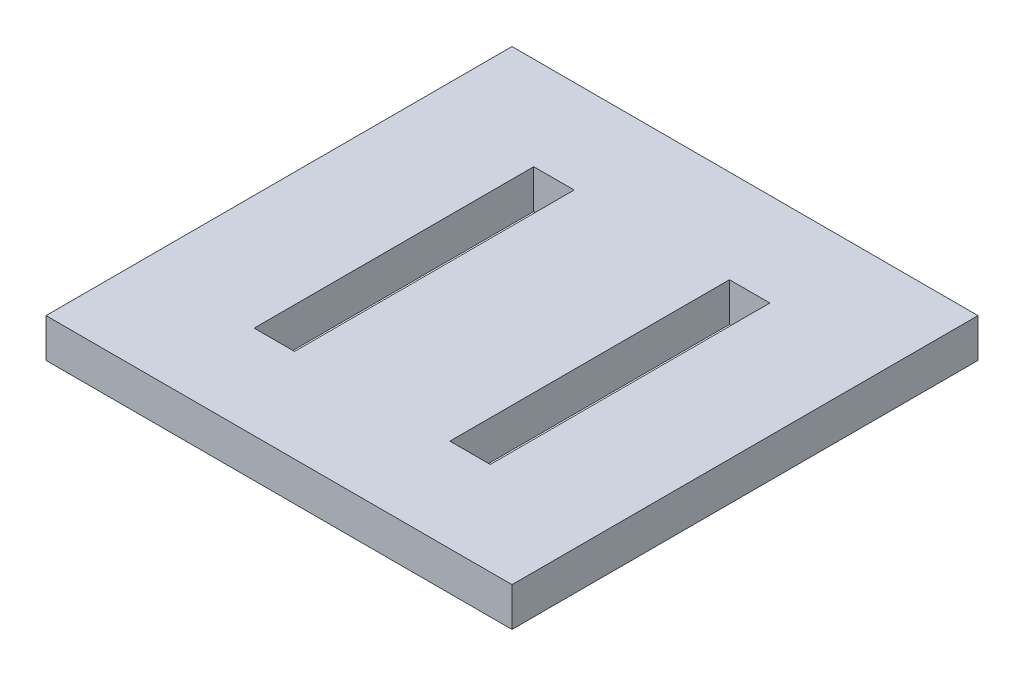
SolidWorks part; units mm, degrees
material "Plain Carbon Steel"
ref_plane "Front Plane" through (0, 0, 0) normal (0, 0, 1) x (1, 0, 0)
ref_plane "Top Plane" through (0, 0, 0) normal (0, 1, 0) x (1, 0, 0)
ref_plane "Right Plane" through (0, 0, 0) normal (1, 0, 0) x (0, 0, -1)
sketch "Sketch1" plane through (0, 0, 0) normal (0, 1, 0) x (1, 0, 0)
  line L1 (-38.1, -38.1) -> (38.1, -38.1)
  line L2 (-38.1, -38.1) -> (-38.1, 38.1)
  line L3 (-38.1, 38.1) -> (38.1, 38.1)
  line L4 (38.1, -38.1) -> (38.1, 38.1)
  line L5 (-38.1, -38.1) -> (38.1, 38.1) construction
  line L6 (-38.1, 38.1) -> (38.1, -38.1) construction
  point P0 (0, 0)
  point P6 (0, 38.1)
  dimension "D1" = 76.2
  dimension "D2" = 76.2
extrude "Boss-Extrude1" add sketch "Sketch1" along normal blind 6.35
sketch "Sketch2" plane through (0, 0, 0) normal (0, 1, 0) x (1, 0, 0)
  line L0 (0, 0) -> (0, 15.412) construction
  line L1 (12.7, -22.86) -> (19.304, -22.86)
  line L2 (12.7, -22.86) -> (12.7, 22.86)
  line L3 (12.7, 22.86) -> (19.304, 22.86)
  line L4 (19.304, -22.86) -> (19.304, 22.86)
  line L5 (12.7, -22.86) -> (19.304, 22.86) construction
  line L6 (12.7, 22.86) -> (19.304, -22.86) construction
  line L7 (-12.7, 22.86) -> (-19.304, -22.86) construction
  line L8 (-12.7, -22.86) -> (-19.304, 22.86) construction
  line L9 (-19.304, -22.86) -> (-19.304, 22.86)
  line L10 (-12.7, 22.86) -> (-19.304, 22.86)
  line L11 (-12.7, -22.86) -> (-12.7, 22.86)
  line L12 (-12.7, -22.86) -> (-19.304, -22.86)
  point P0 (16.002, 0)
  point P13 (-16.002, 0)
  dimension "D1" = 45.72
  dimension "D2" = 6.604
  dimension "D3" = 12.7
extrude "Cut-Extrude1" cut sketch "Sketch2" along normal through all
